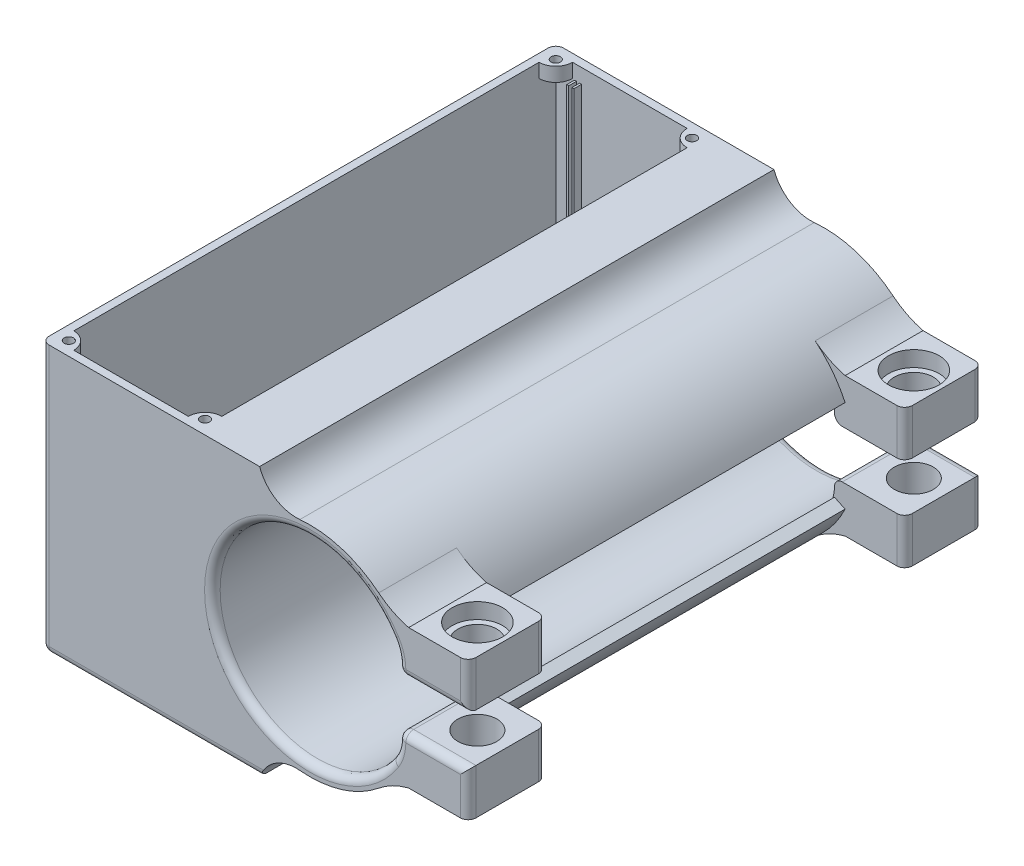
SolidWorks part; units mm, degrees
material "ABS"
ref_plane "Alzado" through (0, 0, 0) normal (0, 0, 1) x (1, 0, 0)
ref_plane "Planta" through (0, 0, 0) normal (0, 1, 0) x (1, 0, 0)
ref_plane "Vista lateral" through (0, 0, 0) normal (1, 0, 0) x (0, 0, -1)
sketch "Croquis1" plane through (0, 0, 0) normal (0, 1, 0) x (1, 0, 0)
  line L0 (0, 0) -> (21, 0)
  line L1 (21, 0) -> (21, 66.01)
  line L2 (21, 66.01) -> (0, 66.01)
  line L3 (20, 65.01) -> (1, 65.01)
  line L4 (20, 65.01) -> (20, 1)
  line L5 (20, 1) -> (1, 1)
  line L6 (0, 66.01) -> (0, 0)
  line L7 (1, 65.01) -> (1, 1)
  dimension "D1" = 1
  dimension "D2" = 1
  dimension "D3" = 1
  dimension "D4" = 1
  dimension "D5" = 64.01
  dimension "D6" = 19
extrude "Saliente-Extruir1" add sketch "Croquis1" along normal blind 34
ref_plane "Plano1" through (0, 0, -66.01) normal (0, 0, -1) x (-1, 0, 0)
sketch "Croquis4" plane through (0, 0, -66.01) normal (0, 0, -1) x (-1, 0, 0)
  line L0 (-21, 0) -> (-21, -0.5)
  line L1 (-21, -0.5) -> (0, -0.5)
  line L2 (0, -0.5) -> (0, 0)
  line L3 (0, 0) -> (-21, 0)
  dimension "D1" = 0.5
extrude "Saliente-Extruir2" add sketch "Croquis4" against normal up to vertex (66.01 mm away)
ref_plane "Plano3" through (0, 0, -1) normal (0, 0, -1) x (-1, 0, 0)
sketch "Croquis5" plane through (0, 0, -1) normal (0, 0, -1) x (-1, 0, 0)
  line L0 (-1, 0) -> (-3.4, 0) construction
  line L1 (-1, 0) -> (-20, 0) construction
  line L3 (-3.4, 0) -> (-3.4, 32.137)
  line L4 (-3.4, 32.137) -> (-3.65, 32.137)
  line L5 (-3.65, 32.137) -> (-3.65, 0)
  line L6 (-3.65, 0) -> (-3.4, 0)
  line L7 (-4.06, 32.137) -> (-4.06, 0)
  line L8 (-4.06, 0) -> (-4.31, 0)
  line L9 (-4.31, 0) -> (-4.31, 32.137)
  line L10 (-4.31, 32.137) -> (-4.06, 32.137)
  dimension "D1" = 2.4
  dimension "D2" = 0.25
  dimension "D3" = 0.41
  dimension "D4" = 0.25
extrude "Saliente-Extruir3" add sketch "Croquis5" along normal blind 1
ref_plane "Plano4" through (0, 0, -65.01) normal (0, 0, 1) x (1, 0, 0)
sketch "Croquis7" plane through (0, 0, -65.01) normal (0, 0, 1) x (1, 0, 0)
  line L0 (4.06, 32.137) -> (4.31, 32.137) construction
  line L1 (4.31, 32.137) -> (4.31, 0) construction
  line L2 (4.31, 0) -> (4.06, 0) construction
  line L3 (4.06, 0) -> (4.06, 32.137) construction
  line L4 (3.65, 0) -> (3.4, 0) construction
  line L5 (3.4, 0) -> (3.4, 32.137) construction
  line L6 (3.4, 32.137) -> (3.65, 32.137) construction
  line L7 (3.65, 32.137) -> (3.65, 0) construction
  line L8 (4.06, 32.137) -> (4.31, 32.137)
  line L9 (4.31, 32.137) -> (4.31, 0)
  line L10 (4.31, 0) -> (4.06, 0)
  line L11 (4.06, 0) -> (4.06, 32.137)
  line L12 (3.65, 0) -> (3.4, 0)
  line L13 (3.4, 0) -> (3.4, 32.137)
  line L14 (3.4, 32.137) -> (3.65, 32.137)
  line L15 (3.65, 32.137) -> (3.65, 0)
extrude "Saliente-Extruir4" add sketch "Croquis7" along normal blind 1
ref_plane "Plano5" through (0, 34, 0) normal (0, 1, 0) x (1, 0, 0)
sketch "Croquis8" plane through (0, 34, 0) normal (0, 1, 0) x (1, 0, 0)
  line L1 (20, 1) -> (20, 65.01) construction
  line L4 (3.15, 1) -> (3.15, 0.4932) construction
  line L8 (1, 3.15) -> (0.4517, 3.15) construction
  line L10 (17.85, 1) -> (20, 1)
  line L16 (1, 65.01) -> (1, 1) construction
  line L17 (1, 1) -> (20, 1) construction
  line L18 (20, 1) -> (20, 3.15)
  line L19 (3.15, 1) -> (1, 1)
  line L20 (1, 1) -> (1, 3.15)
  line L21 (1, 1) -> (2.5203, 2.5203) construction
  line L22 (20, 1) -> (18.4797, 2.5203) construction
  line L23 (20, 65.01) -> (1, 65.01) construction
  line L24 (1, 62.86) -> (1, 65.01)
  line L25 (1, 65.01) -> (3.15, 65.01)
  line L26 (1, 65.01) -> (2.5203, 63.4897) construction
  line L27 (20, 62.86) -> (20, 65.01)
  line L28 (20, 65.01) -> (17.85, 65.01)
  line L29 (20, 65.01) -> (18.4797, 63.4897) construction
  arc A25 (17.85, 1) -> (20, 3.15) centre (20, 1) cw
  circle A26 centre (19.2399, 1.7601) radius 0.6
  arc A27 (17.85, 65.01) -> (20, 62.86) centre (20, 65.01) ccw
  circle A28 centre (19.2399, 64.2499) radius 0.6
  arc A29 (1, 62.86) -> (3.15, 65.01) centre (1, 65.01) ccw
  circle A30 centre (1.7601, 64.2499) radius 0.6
  arc A31 (3.15, 1) -> (1, 3.15) centre (1, 1) ccw
  circle A32 centre (1.7601, 1.7601) radius 0.6
  dimension "D2" = 2.15
  dimension "D3" = 1.2
  dimension "D7" = 2.15
  dimension "D8" = 2.15
  dimension "D4" = 2.15
  dimension "D6" = 1.2
  dimension "D9" = 1.2
  dimension "D12" = 1.2
  dimension "D1" = 2.15
  dimension "D5" = 2.15
  dimension "D10" = 2.15
  dimension "D11" = 2.15
extrude "Saliente-Extruir5" add sketch "Croquis8" against normal blind 1.8
ref_plane "Plano6" through (21, 0, 0) normal (1, 0, 0) x (0, 0, -1)
ref_plane "Plano7" through (21, 0, 0) normal (1, 0, 0) x (0, 0, -1)
sketch "Croquis13" plane through (21, 0, 0) normal (1, 0, 0) x (0, 0, -1)
  line L1 (0, 34) -> (66.01, 34)
  line L2 (0, 34) -> (0, -0.5)
  line L3 (0, -0.5) -> (66.01, -0.5)
  line L4 (66.01, 34) -> (66.01, -0.5)
extrude "Saliente-Extruir6" add sketch "Croquis13" along normal blind 7
ref_plane "Plano8" through (0, 0, -66.01) normal (0, 0, -1) x (-1, 0, 0)
sketch "Croquis14" plane through (0, 0, -66.01) normal (0, 0, -1) x (-1, 0, 0)
  line L0 (-28, 16.75) -> (-14.9428, 16.75) construction
  line L5 (-28, -0.5) -> (-28, 34) construction
  line L6 (-28, 16.75) -> (-35.253, 16.75) construction
  line L9 (-28, 27.4653) -> (-28, 6.0347)
  circle A4 centre (-34.4367, 16.75) radius 12.5 construction
  arc A8 (-28, 27.4653) -> (-28, 6.0347) centre (-34.4367, 16.75) cw
  dimension "D1" = 25
extrude "Cortar-Extruir1" cut sketch "Croquis14" against normal through all
ref_plane "Plano9" through (0, 0, 0) normal (0, 0, 1) x (1, 0, 0)
sketch "Croquis15" plane through (0, 0, 0) normal (0, 0, 1) x (1, 0, 0)
  line L0 (34.4367, 16.75) -> (21.9367, 16.75) construction
  line L1 (45.7656, 22.0327) -> (45.7656, 11.4673) construction
  line L2 (34.4367, 16.75) -> (45.7656, 11.4673) construction
  line L3 (45.7656, 11.4673) -> (47.125, 10.8333) construction
  line L4 (34.4367, 16.75) -> (45.7656, 22.0327) construction
  line L5 (45.7656, 22.0327) -> (47.125, 22.6667) construction
  line L6 (34.4367, 16.75) -> (28, 6.0347) construction
  line L7 (28, 6.0347) -> (27.2276, 4.7488) construction
  line L8 (34.4367, 16.75) -> (28, 27.4653) construction
  line L9 (28, 27.4653) -> (26.1952, 30.4699) construction
  line L10 (47.125, 22.6667) -> (45.7656, 22.0327)
  line L11 (28, 34) -> (28, 29.1826) construction
  line L12 (28, 34) -> (28, 27.4653) construction
  line L13 (28, 29.1826) -> (28, 27.4653)
  line L14 (28, 6.0347) -> (28, -0.5) construction
  line L15 (47.125, 10.8333) -> (45.7656, 11.4673)
  line L16 (28, 4.3174) -> (28, 6.0347)
  circle A0 centre (34.4367, 16.75) radius 12.5 construction
  circle A1 centre (34.4367, 16.75) radius 12.5 construction
  arc A2 (28, 27.4653) -> (45.7656, 22.0327) centre (34.4367, 16.75) cw
  arc A3 (45.7656, 11.4673) -> (28, 6.0347) centre (34.4367, 16.75) cw
  arc A4 (47.125, 22.6667) -> (28, 29.1826) centre (34.4367, 16.75) ccw
  arc A5 (47.125, 10.8333) -> (28, 4.3174) centre (34.4367, 16.75) cw
  dimension "D1" = 1.5
  dimension "D2" = 25
  dimension "D3" = 1.5
  dimension "D4" = 1.5
extrude "Saliente-Extruir8" add sketch "Croquis15" against normal through all
sketch "Croquis16" plane through (0, 0, -66.01) normal (0, 0, -1) x (-1, 0, 0)
  line L0 (-34.4367, 16.75) -> (-60.2289, 16.75) construction
  line L1 (-45.7656, 11.4673) -> (-45.7656, 13.6673)
  line L2 (-45.7656, 13.6673) -> (-54.7656, 13.6673)
  line L3 (-47.125, 10.8333) -> (-54.7656, 10.8333)
  line L4 (-54.7656, 10.8333) -> (-54.7656, 13.6673)
  line L5 (-45.7656, 11.4673) -> (-47.125, 10.8333)
  line L6 (-45.7656, 22.0327) -> (-45.7656, 19.8327)
  line L7 (-45.7656, 22.0327) -> (-47.125, 22.6667)
  line L8 (-47.125, 22.6667) -> (-54.7656, 22.6667)
  line L9 (-54.7656, 22.6667) -> (-54.7656, 19.8327)
  line L10 (-54.7656, 19.8327) -> (-45.7656, 19.8327)
  dimension "D1" = 2.2
  dimension "D2" = 9
  dimension "D3" = 2.2
  dimension "D4" = 9
extrude "Saliente-Extruir9" add sketch "Croquis16" against normal blind 10
sketch "Croquis17" plane through (0, 0, 0) normal (0, 0, 1) x (1, 0, 0)
  line L0 (45.7656, 11.4673) -> (47.125, 10.8333) construction
  line L1 (47.125, 10.8333) -> (54.7656, 10.8333) construction
  line L2 (54.7656, 10.8333) -> (54.7656, 13.6673) construction
  line L3 (54.7656, 13.6673) -> (45.7656, 13.6673) construction
  line L4 (45.7656, 13.6673) -> (45.7656, 11.4673) construction
  line L5 (47.125, 22.6667) -> (45.7656, 22.0327) construction
  line L6 (45.7656, 22.0327) -> (45.7656, 19.8327) construction
  line L7 (45.7656, 19.8327) -> (54.7656, 19.8327) construction
  line L8 (54.7656, 19.8327) -> (54.7656, 22.6667) construction
  line L9 (54.7656, 22.6667) -> (47.125, 22.6667) construction
  line L10 (45.7656, 11.4673) -> (47.125, 10.8333)
  line L11 (47.125, 10.8333) -> (54.7656, 10.8333)
  line L12 (54.7656, 10.8333) -> (54.7656, 13.6673)
  line L13 (54.7656, 13.6673) -> (45.7656, 13.6673)
  line L14 (45.7656, 13.6673) -> (45.7656, 11.4673)
  line L15 (47.125, 22.6667) -> (45.7656, 22.0327)
  line L16 (45.7656, 22.0327) -> (45.7656, 19.8327)
  line L17 (45.7656, 19.8327) -> (54.7656, 19.8327)
  line L18 (54.7656, 19.8327) -> (54.7656, 22.6667)
  line L19 (54.7656, 22.6667) -> (47.125, 22.6667)
extrude "Saliente-Extruir10" add sketch "Croquis17" against normal blind 10
ref_plane "Plano10" through (0, 22.6667, 0) normal (0, 1, 0) x (1, 0, 0)
sketch "Croquis21" plane through (0, 22.6667, 0) normal (0, 1, 0) x (1, 0, 0)
  line L0 (47.125, 56.01) -> (54.7656, 56.01) construction
  line L1 (54.7656, 56.01) -> (54.7656, 66.01) construction
  line L2 (47.125, 66.01) -> (54.7656, 66.01) construction
  line L3 (47.125, 66.01) -> (47.125, 56.01) construction
  line L4 (54.7656, 10) -> (54.7656, 0) construction
  line L5 (54.7656, 10) -> (47.125, 10) construction
  line L6 (47.125, 10) -> (47.125, 0) construction
  line L7 (54.7656, 0) -> (47.125, 0) construction
  line L8 (47.125, 56.01) -> (54.7656, 56.01)
  line L9 (54.7656, 56.01) -> (54.7656, 66.01)
  line L10 (47.125, 66.01) -> (54.7656, 66.01)
  line L11 (47.125, 66.01) -> (47.125, 56.01)
  line L12 (54.7656, 10) -> (54.7656, 0)
  line L13 (54.7656, 10) -> (47.125, 10)
  line L14 (47.125, 10) -> (47.125, 0)
  line L15 (54.7656, 0) -> (47.125, 0)
extrude "Saliente-Extruir12" add sketch "Croquis21" along normal blind 3
ref_plane "Plano11" through (0, 10.8333, 0) normal (0, -1, 0) x (-1, 0, 0)
sketch "Croquis22" plane through (0, 10.8333, 0) normal (0, -1, 0) x (-1, 0, 0)
  line L0 (-54.7656, 10) -> (-54.7656, 0) construction
  line L1 (-47.125, 10) -> (-54.7656, 10) construction
  line L2 (-47.125, 10) -> (-47.125, 0) construction
  line L3 (-47.125, 0) -> (-54.7656, 0) construction
  line L4 (-54.7656, 66.01) -> (-47.125, 66.01) construction
  line L5 (-54.7656, 56.01) -> (-54.7656, 66.01) construction
  line L6 (-54.7656, 56.01) -> (-47.125, 56.01) construction
  line L7 (-47.125, 66.01) -> (-47.125, 56.01) construction
  line L8 (-54.7656, 10) -> (-54.7656, 0)
  line L9 (-47.125, 10) -> (-54.7656, 10)
  line L10 (-47.125, 10) -> (-47.125, 0)
  line L11 (-47.125, 0) -> (-54.7656, 0)
  line L12 (-54.7656, 66.01) -> (-47.125, 66.01)
  line L13 (-54.7656, 56.01) -> (-54.7656, 66.01)
  line L14 (-54.7656, 56.01) -> (-47.125, 56.01)
  line L15 (-47.125, 66.01) -> (-47.125, 56.01)
extrude "Saliente-Extruir13" add sketch "Croquis22" along normal blind 3
ref_plane "Plano12" through (0, 25.6667, 0) normal (0, 1, 0) x (1, 0, 0)
sketch "Croquis23" plane through (0, 25.6667, 0) normal (0, 1, 0) x (1, 0, 0)
  line L0 (47.125, 66.01) -> (54.7656, 56.01) construction
  line L1 (47.125, 10) -> (54.7656, 0) construction
  circle A0 centre (50.9453, 61.01) radius 2.5
  circle A1 centre (50.9453, 5) radius 2.5
  dimension "D1" = 5
extrude "Cortar-Extruir2" cut sketch "Croquis23" against normal through all
sketch "Croquis24" plane through (0, 25.6667, 0) normal (0, 1, 0) x (1, 0, 0)
  circle A0 centre (50.9453, 5) radius 3.25
  circle A1 centre (50.9453, 61.01) radius 3.25
  dimension "D1" = 6.5
  dimension "D2" = 6.5
extrude "Cortar-Extruir3" cut sketch "Croquis24" against normal blind 2
ref_plane "Plano13" through (0, 7.8333, 0) normal (0, -1, 0) x (-1, 0, 0)
sketch "Croquis26" plane through (0, 7.8333, 0) normal (0, -1, 0) x (-1, 0, 0)
  circle A0 centre (-50.9453, 61.01) radius 3.25
  circle A1 centre (-50.9453, 5) radius 3.25
  dimension "D1" = 6.5
  dimension "D2" = 6.5
extrude "Cortar-Extruir4" cut sketch "Croquis26" against normal blind 2
fillet "Redondeo1" radius 10 4 edges at (47.125, 22.6667, -5) (47.125, 10.8333, -5) (47.125, 10.8333, -61.01) (47.125, 22.6667, -61.01)
fillet "Redondeo2" radius 5 4 edges at (45.7656, 11.4673, -5) (45.7656, 11.4673, -61.01) (45.7656, 22.0327, -5) (45.7656, 22.0327, -61.01)
fillet "Redondeo3" radius 5 2 edges at (28, 29.1826, -33.005) (28, 4.3174, -33.005)
fillet "Redondeo4" radius 1 5 edges at (14, -0.5, -66.01) (14, -0.5, 0) (0, 16.75, -66.01) (0, -0.5, -33.005) (0, 16.75, 0)
fillet "Redondeo5" radius 1 4 edges at (45.7656, 13.6673, -5) (45.7656, 19.8327, -5) (45.7656, 13.6673, -61.01) (45.7656, 19.8327, -61.01)
fillet "Redondeo6" radius 1 22 edges at (50.7654, 13.6673, 0) (46.0616, 13.3778, 0) (45.5596, 11.3052, 0) (21.9367, 16.75, 0) (50.7654, 19.8327, 0) (46.0616, 20.1222, 0) (50.7654, 19.8327, -66.01) (46.0616, 20.1222, -66.01) (45.5596, 22.1948, -66.01) (21.9367, 16.75, -66.01) (50.7654, 13.6673, -66.01) (46.0616, 13.3778, -66.01) (45.5596, 22.1948, 0) (45.5596, 11.3052, -66.01) (54.7656, 22.7497, -66.01) (54.7656, 22.7497, -56.01) (54.7656, 10.7503, -56.01) (54.7656, 10.7503, -66.01) (54.7656, 22.7497, -10) (54.7656, 22.7497, 0) (54.7656, 10.7503, 0) (54.7656, 10.7503, -10)
